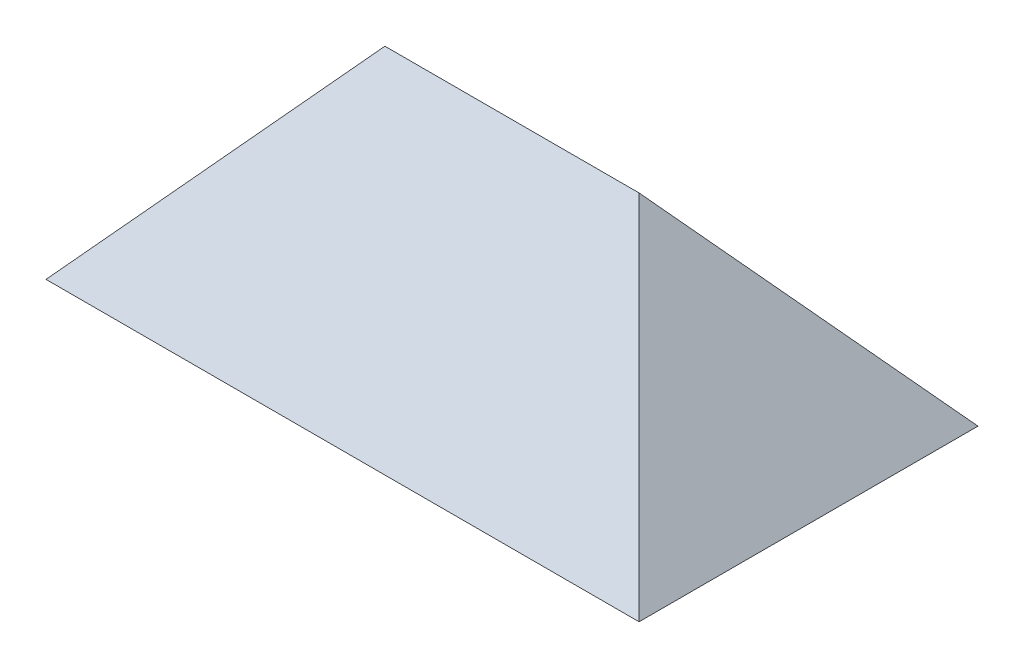
SolidWorks part; units mm, degrees
ref_plane "Front Plane" through (0, 0, 0) normal (0, 0, 1) x (1, 0, 0)
ref_plane "Top Plane" through (0, 0, 0) normal (0, 1, 0) x (1, 0, 0)
ref_plane "Right Plane" through (0, 0, 0) normal (1, 0, 0) x (0, 0, -1)
sketch "Sketch1" plane through (0, 0, 0) normal (0, 0, 1) x (1, 0, 0)
  line L0 (0, 0) -> (0, 125.1341) construction
  line L1 (0, 125.1341) -> (105, 0)
  line L2 (105, 0) -> (0, 0)
  line L3 (0, 0) -> (-105, 0)
  line L4 (-105, 0) -> (0, 125.1341)
  line L5 (-105, 0) -> (-105, 10) construction
  dimension "D1" = 210
  dimension "D2" = 105
  dimension "D3" = 40
  dimension "D4" = 10
extrude "Boss-Extrude2" add sketch "Sketch1" along normal blind 120
sketch "Sketch4" plane through (0, 0, 0) normal (1, 0, 0) x (0, 0, -1)
  line L0 (-120, 0) -> (-60, 71.5052)
  line L1 (-60, 71.5052) -> (0, 0)
  line L2 (0, 0) -> (0, 135.1341)
  line L3 (0, 135.1341) -> (-120, 135.1341)
  line L4 (-120, 135.1341) -> (-120, 0)
  line L5 (-120, 125.1341) -> (0, 125.1341) construction
  dimension "D1" = 40
  dimension "D2" = 40
  dimension "D3" = 10
extrude "Cut-Extrude3" cut sketch "Sketch4" against normal mid plane 300
shell "Shell3" thickness 4 removed face at (0, 0, 60)
